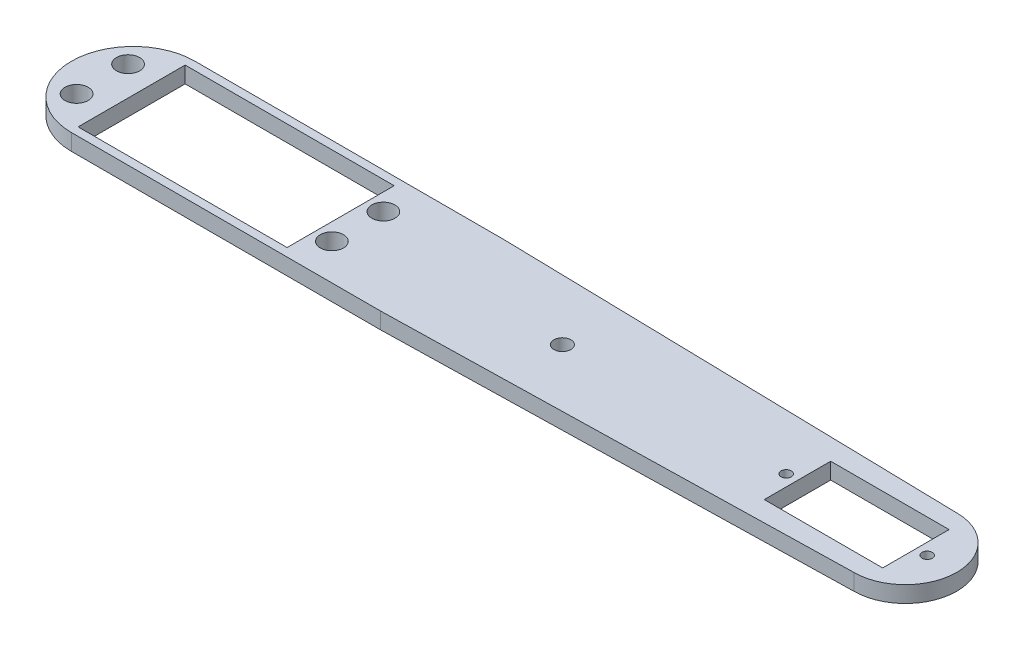
SolidWorks part; units mm, degrees
ref_plane "Front Plane" through (0, 0, 0) normal (0, 0, 1) x (1, 0, 0)
ref_plane "Top Plane" through (0, 0, 0) normal (0, 1, 0) x (1, 0, 0)
ref_plane "Right Plane" through (0, 0, 0) normal (1, 0, 0) x (0, 0, -1)
sketch "Sketch1" plane through (0, 0, 0) normal (0, 1, 0) x (1, 0, 0)
  line L0 (-142.4345, 14.2447) -> (-82.4345, 14.2447)
  line L1 (-82.4345, 14.2447) -> (7.5655, 12.2447)
  line L2 (-142.4345, -9.7553) -> (-82.4345, -9.7553)
  line L3 (-82.4345, -9.7553) -> (7.5655, -7.7553)
  line L4 (-148.4345, 19.311) -> (-148.4345, -13.0468) construction
  line L5 (-15.5874, 2.2447) -> (11.8126, 2.2447) construction
  line L6 (-142.7397, -8.1553) -> (-102.1397, -8.1553)
  line L7 (-142.7397, -8.1553) -> (-142.7397, 12.6447)
  line L8 (-142.7397, 12.6447) -> (-102.1397, 12.6447)
  line L9 (-102.1397, -8.1553) -> (-102.1397, 12.6447)
  line L10 (-13.3874, 8.6947) -> (9.6126, 8.6947)
  line L11 (-13.3874, 8.6947) -> (-13.3874, -4.2053)
  line L12 (-13.3874, -4.2053) -> (9.6126, -4.2053)
  line L13 (9.6126, 8.6947) -> (9.6126, -4.2053)
  line L14 (-13.3874, 8.6947) -> (9.6126, -4.2053) construction
  line L15 (-13.3874, -4.2053) -> (9.6126, 8.6947) construction
  arc A0 (-142.4345, 14.2447) -> (-142.4345, -9.7553) centre (-142.4345, 2.2447) ccw
  arc A1 (7.5655, -7.7553) -> (7.5655, 12.2447) centre (7.5655, 2.2447) ccw
  circle A3 centre (-148.4345, 7.2447) radius 2.25
  circle A4 centre (-148.4345, -2.7553) radius 2.25
  circle A5 centre (-98.8345, 7.2447) radius 2.25
  circle A6 centre (-98.8345, -2.7553) radius 2.25
  circle A7 centre (-15.5874, 2.2447) radius 1
  circle A8 centre (11.8126, 2.2447) radius 1
  circle A9 centre (-59.0553, 2.2447) radius 1.65
  point P20 (-1.8874, 2.2447)
  dimension "D6" = 4.5
  dimension "D17" = 2
  dimension "D18" = 3.3
  dimension "D2" = 24
  dimension "D3" = 20
  dimension "D4" = 5
  dimension "D5" = 5
  dimension "D7" = 49.6
  dimension "D8" = 60
  dimension "D9" = 150
  dimension "D10" = 6
  dimension "D11" = 0
  dimension "D12" = 20.8
  dimension "D13" = 40.6
  dimension "D14" = 12.9
  dimension "D15" = 23
  dimension "D16" = 27.4
extrude "Boss-Extrude1" add sketch "Sketch1" along normal blind 3.175
equation "\"D5@Sketch1\"=\"D4@Sketch1\""
